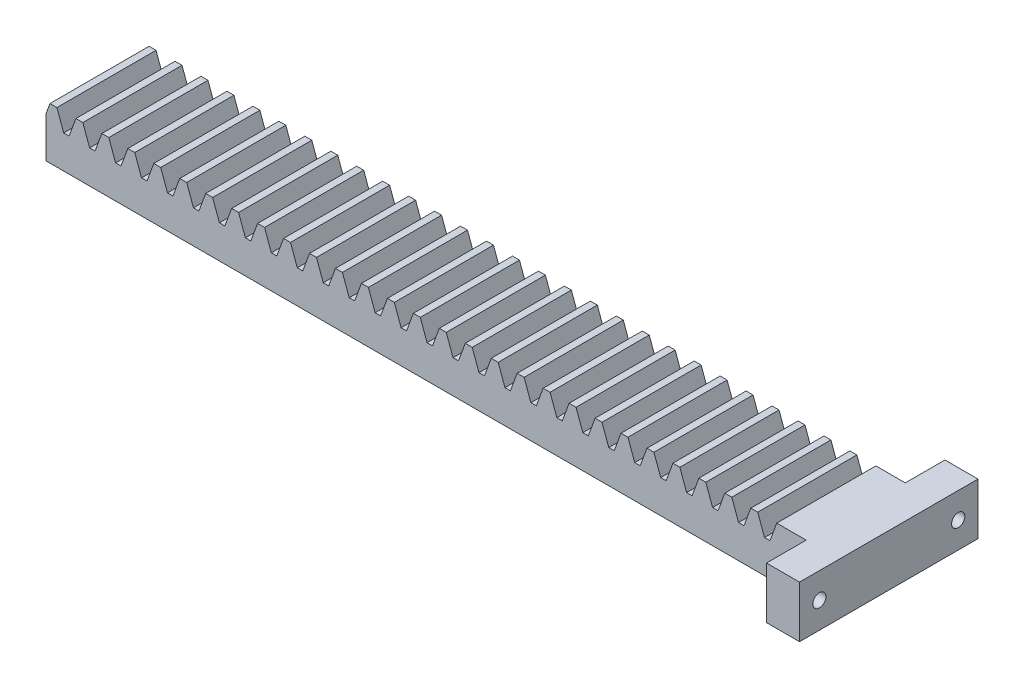
SolidWorks part; units mm, degrees
ref_plane "Front Plane" through (0, 0, 0) normal (0, 0, 1) x (1, 0, 0)
ref_plane "Top Plane" through (0, 0, 0) normal (0, 1, 0) x (1, 0, 0)
ref_plane "Right Plane" through (0, 0, 0) normal (1, 0, 0) x (0, 0, -1)
sketch "Sketch1" plane through (0, 0, 0) normal (0, 0, 1) x (1, 0, 0)
  line L0 (110, 7.8125) -> (110, -7.8125)
  line L1 (110, -7.8125) -> (120, -7.8125)
  line L2 (120, -7.8125) -> (120, 7.8125)
  line L3 (120, 7.8125) -> (110, 7.8125)
  line L4 (110, -7.8125) -> (110, 7.8125)
  line L5 (110, 7.8125) -> (101.1016, 7.8125)
  line L6 (101.1016, 7.8125) -> (99.0542, 2.1875)
  line L7 (99.0542, 2.1875) -> (97.402, 2.1875)
  line L8 (97.402, 2.1875) -> (95.3547, 7.8125)
  line L9 (95.3547, 7.8125) -> (93.2476, 7.8125)
  line L10 (93.2476, 7.8125) -> (91.2002, 2.1875)
  line L11 (91.2002, 2.1875) -> (89.548, 2.1875)
  line L12 (89.548, 2.1875) -> (87.5007, 7.8125)
  line L13 (87.5007, 7.8125) -> (85.3936, 7.8125)
  line L14 (85.3936, 7.8125) -> (83.3462, 2.1875)
  line L15 (83.3462, 2.1875) -> (81.694, 2.1875)
  line L16 (81.694, 2.1875) -> (79.6467, 7.8125)
  line L17 (79.6467, 7.8125) -> (77.5396, 7.8125)
  line L18 (77.5396, 7.8125) -> (75.4922, 2.1875)
  line L19 (75.4922, 2.1875) -> (73.84, 2.1875)
  line L20 (73.84, 2.1875) -> (71.7927, 7.8125)
  line L21 (71.7927, 7.8125) -> (69.6856, 7.8125)
  line L22 (69.6856, 7.8125) -> (67.6382, 2.1875)
  line L23 (67.6382, 2.1875) -> (65.986, 2.1875)
  line L24 (65.986, 2.1875) -> (63.9387, 7.8125)
  line L25 (63.9387, 7.8125) -> (61.8316, 7.8125)
  line L26 (61.8316, 7.8125) -> (59.7842, 2.1875)
  line L27 (59.7842, 2.1875) -> (58.132, 2.1875)
  line L28 (58.132, 2.1875) -> (56.0847, 7.8125)
  line L29 (56.0847, 7.8125) -> (53.9776, 7.8125)
  line L30 (53.9776, 7.8125) -> (51.9302, 2.1875)
  line L31 (51.9302, 2.1875) -> (50.278, 2.1875)
  line L32 (50.278, 2.1875) -> (48.2307, 7.8125)
  line L33 (48.2307, 7.8125) -> (46.1236, 7.8125)
  line L34 (46.1236, 7.8125) -> (44.0762, 2.1875)
  line L35 (44.0762, 2.1875) -> (42.424, 2.1875)
  line L36 (42.424, 2.1875) -> (40.3767, 7.8125)
  line L37 (40.3767, 7.8125) -> (38.2696, 7.8125)
  line L38 (38.2696, 7.8125) -> (36.2222, 2.1875)
  line L39 (36.2222, 2.1875) -> (34.57, 2.1875)
  line L40 (34.57, 2.1875) -> (32.5227, 7.8125)
  line L41 (32.5227, 7.8125) -> (30.4156, 7.8125)
  line L42 (30.4156, 7.8125) -> (28.3682, 2.1875)
  line L43 (28.3682, 2.1875) -> (26.716, 2.1875)
  line L44 (26.716, 2.1875) -> (24.6687, 7.8125)
  line L45 (24.6687, 7.8125) -> (22.5616, 7.8125)
  line L46 (22.5616, 7.8125) -> (20.5142, 2.1875)
  line L47 (20.5142, 2.1875) -> (18.862, 2.1875)
  line L48 (18.862, 2.1875) -> (16.8147, 7.8125)
  line L49 (16.8147, 7.8125) -> (14.7076, 7.8125)
  line L50 (14.7076, 7.8125) -> (12.6602, 2.1875)
  line L51 (12.6602, 2.1875) -> (11.008, 2.1875)
  line L52 (11.008, 2.1875) -> (8.9607, 7.8125)
  line L53 (8.9607, 7.8125) -> (6.8536, 7.8125)
  line L54 (6.8536, 7.8125) -> (4.8062, 2.1875)
  line L55 (4.8062, 2.1875) -> (3.154, 2.1875)
  line L56 (3.154, 2.1875) -> (1.1067, 7.8125)
  line L57 (1.1067, 7.8125) -> (-1.0004, 7.8125)
  line L58 (-1.0004, 7.8125) -> (-3.0478, 2.1875)
  line L59 (-3.0478, 2.1875) -> (-4.7, 2.1875)
  line L60 (-4.7, 2.1875) -> (-6.7473, 7.8125)
  line L61 (-6.7473, 7.8125) -> (-8.8544, 7.8125)
  line L62 (-8.8544, 7.8125) -> (-10.9018, 2.1875)
  line L63 (-10.9018, 2.1875) -> (-12.554, 2.1875)
  line L64 (-12.554, 2.1875) -> (-14.6013, 7.8125)
  line L65 (-14.6013, 7.8125) -> (-16.7084, 7.8125)
  line L66 (-16.7084, 7.8125) -> (-18.7558, 2.1875)
  line L67 (-18.7558, 2.1875) -> (-20.408, 2.1875)
  line L68 (-20.408, 2.1875) -> (-22.4553, 7.8125)
  line L69 (-22.4553, 7.8125) -> (-24.5624, 7.8125)
  line L70 (-24.5624, 7.8125) -> (-26.6098, 2.1875)
  line L71 (-26.6098, 2.1875) -> (-28.262, 2.1875)
  line L72 (-28.262, 2.1875) -> (-30.3093, 7.8125)
  line L73 (-30.3093, 7.8125) -> (-32.4164, 7.8125)
  line L74 (-32.4164, 7.8125) -> (-34.4638, 2.1875)
  line L75 (-34.4638, 2.1875) -> (-36.116, 2.1875)
  line L76 (-36.116, 2.1875) -> (-38.1633, 7.8125)
  line L77 (-38.1633, 7.8125) -> (-40.2704, 7.8125)
  line L78 (-40.2704, 7.8125) -> (-42.3178, 2.1875)
  line L79 (-42.3178, 2.1875) -> (-43.97, 2.1875)
  line L80 (-43.97, 2.1875) -> (-46.0173, 7.8125)
  line L81 (-46.0173, 7.8125) -> (-48.1244, 7.8125)
  line L82 (-48.1244, 7.8125) -> (-50.1718, 2.1875)
  line L83 (-50.1718, 2.1875) -> (-51.824, 2.1875)
  line L84 (-51.824, 2.1875) -> (-53.8713, 7.8125)
  line L85 (-53.8713, 7.8125) -> (-55.9784, 7.8125)
  line L86 (-55.9784, 7.8125) -> (-58.0258, 2.1875)
  line L87 (-58.0258, 2.1875) -> (-59.678, 2.1875)
  line L88 (-59.678, 2.1875) -> (-61.7253, 7.8125)
  line L89 (-61.7253, 7.8125) -> (-63.8324, 7.8125)
  line L90 (-63.8324, 7.8125) -> (-65.8798, 2.1875)
  line L91 (-65.8798, 2.1875) -> (-67.532, 2.1875)
  line L92 (-67.532, 2.1875) -> (-69.5793, 7.8125)
  line L93 (-69.5793, 7.8125) -> (-71.6864, 7.8125)
  line L94 (-71.6864, 7.8125) -> (-73.7338, 2.1875)
  line L95 (-73.7338, 2.1875) -> (-75.386, 2.1875)
  line L96 (-75.386, 2.1875) -> (-77.4333, 7.8125)
  line L97 (-77.4333, 7.8125) -> (-79.5404, 7.8125)
  line L98 (-79.5404, 7.8125) -> (-81.5878, 2.1875)
  line L99 (-81.5878, 2.1875) -> (-83.24, 2.1875)
  line L100 (-83.24, 2.1875) -> (-85.2873, 7.8125)
  line L101 (-85.2873, 7.8125) -> (-87.3944, 7.8125)
  line L102 (-87.3944, 7.8125) -> (-89.4418, 2.1875)
  line L103 (-89.4418, 2.1875) -> (-91.094, 2.1875)
  line L104 (-91.094, 2.1875) -> (-93.1413, 7.8125)
  line L105 (-93.1413, 7.8125) -> (-95.2484, 7.8125)
  line L106 (-95.2484, 7.8125) -> (-97.2958, 2.1875)
  line L107 (-97.2958, 2.1875) -> (-98.948, 2.1875)
  line L108 (-98.948, 2.1875) -> (-100.9953, 7.8125)
  line L109 (-100.9953, 7.8125) -> (-103.1024, 7.8125)
  line L110 (-103.1024, 7.8125) -> (-105.1498, 2.1875)
  line L111 (-105.1498, 2.1875) -> (-106.802, 2.1875)
  line L112 (-106.802, 2.1875) -> (-108.8493, 7.8125)
  line L113 (-108.8493, 7.8125) -> (-110.9564, 7.8125)
  line L114 (-110.9564, 7.8125) -> (-113.0038, 2.1875)
  line L115 (-113.0038, 2.1875) -> (-114.656, 2.1875)
  line L116 (-114.656, 2.1875) -> (-116.7033, 7.8125)
  line L117 (-116.7033, 7.8125) -> (-118.8104, 7.8125)
  line L118 (-118.8104, 7.8125) -> (-120, 4.5442)
  line L119 (-120, 4.5442) -> (-120, -7.8125)
  line L120 (-120, -7.8125) -> (110, -7.8125)
extrude "Boss-Extrude1" add sketch "Sketch1" along normal mid plane 30 contours L119 L120 L0 L5 L6 L7 L8 L9 L10 L11 L12 L13 L14 L15 L16 L17 L18 L19 L20 L21 L22 L23 L24 L25 L26 L27 L28 L29 L30 L31 L32 L33 L34 L35 L36 L37 L38 L39 L40 L41 L42 L43 L44 L45 L46 L47 L48 L49 L50 L51 L52 region at (-4.3836, -1.073, 0)
extrude "Boss-Extrude2" add sketch "Sketch1<3>" along normal mid plane 54 contours L2 L3 L0 L1 region at (115, 0, 0)
sketch "Sketch1<3>" plane through (0, 0, 0) normal (0, 0, 1) x (1, 0, 0) same geometry as "Sketch1"
sketch "Sketch2" plane through (120, 0, 0) normal (1, 0, 0) x (0, 0, -1)
  line L0 (26.9975, 7.8553) -> (-27.0025, 7.8553)
  line L1 (-27.0025, 7.8553) -> (-27.0025, -7.7697)
  line L2 (-27.0025, -7.7697) -> (26.9975, -7.7697)
  line L3 (26.9975, -7.7697) -> (26.9975, 7.8553)
  line L4 (27, -7.8125) -> (27, 7.8125) construction
  line L5 (-27, 7.8125) -> (27, 7.8125) construction
  circle A0 centre (21.0125, 0.0428) radius 2
  circle A1 centre (-21.0025, 0.0428) radius 2
  dimension "D1" = 4
  dimension "D2" = 0.0025
  dimension "D3" = 5.9875
  dimension "D4" = 48.0025
  dimension "D5" = 54.0025
  dimension "D6" = 0.0428
  dimension "D7" = 7.7697
  dimension "D8" = 15.5822
extrude "Cut-Extrude1" cut sketch "Sketch2" against normal blind 54 contours A1 | A0 region at (120, 0.0428, -21.0125) region at (120, 0.0428, 21.0025)
